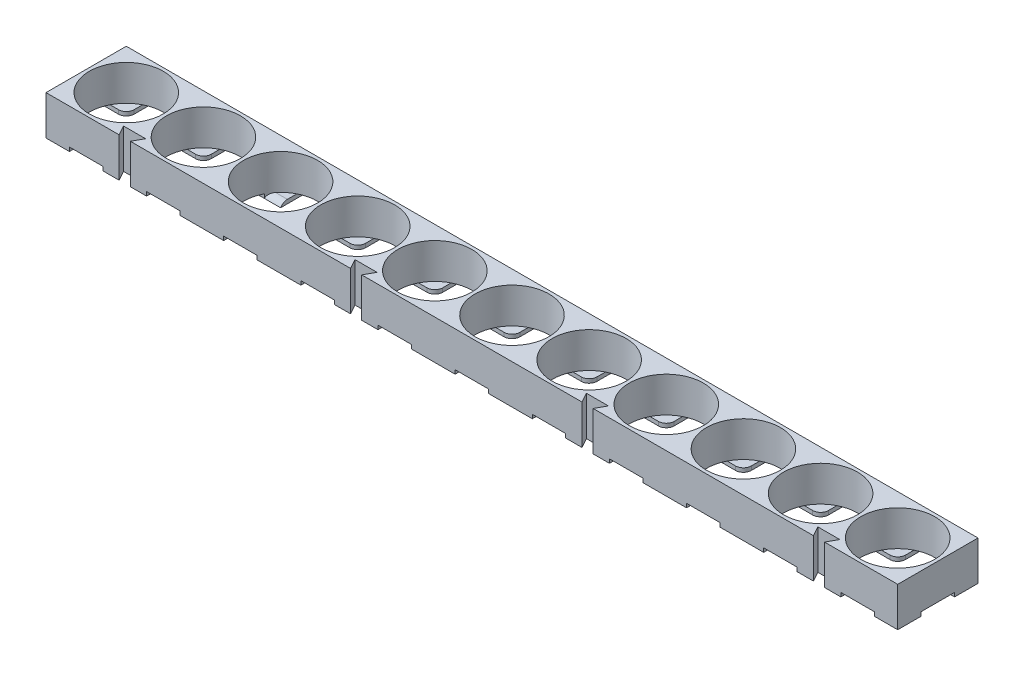
SolidWorks part; units mm, degrees
note: The reader was unsure of these and kept them because the rebuilt part matched: shared geometry of "Sketch3<4>".
ref_plane "Front Plane" through (0, 0, 0) normal (0, 0, 1) x (1, 0, 0)
ref_plane "Top Plane" through (0, 0, 0) normal (0, 1, 0) x (1, 0, 0)
ref_plane "Right Plane" through (0, 0, 0) normal (1, 0, 0) x (0, 0, -1)
sketch "Sketch3" plane through (0, 0, 0) normal (0, 1, 0) x (1, 0, 0)
  line L0 (-10.2, 0) -> (9.4, 0) construction
  line L5 (9.4, 9.4) -> (9.4, -9.4) construction
  line L6 (9.4, -9.4) -> (-9.4, -9.4) construction
  line L7 (-9.4, -9.4) -> (-9.4, 9.4) construction
  line L8 (-9.4, 9.4) -> (9.4, 9.4) construction
  line L9 (10.2, -9.4) -> (10.2, 9.4) construction
  line L10 (10.2, 9.4) -> (29, 9.4) construction
  line L11 (29, 9.4) -> (29, -9.4) construction
  line L12 (29, -9.4) -> (10.2, -9.4) construction
  line L13 (29.8, -9.4) -> (29.8, 9.4) construction
  line L14 (29.8, 9.4) -> (48.6, 9.4) construction
  line L15 (48.6, 9.4) -> (48.6, -9.4) construction
  line L16 (48.6, -9.4) -> (29.8, -9.4) construction
  line L17 (49.4, -9.4) -> (49.4, 9.4) construction
  line L18 (49.4, 9.4) -> (68.2, 9.4) construction
  line L19 (68.2, 9.4) -> (68.2, -9.4) construction
  line L20 (68.2, -9.4) -> (49.4, -9.4) construction
  line L21 (69, -9.4) -> (69, 9.4) construction
  line L22 (69, 9.4) -> (87.8, 9.4) construction
  line L23 (87.8, 9.4) -> (87.8, -9.4) construction
  line L24 (87.8, -9.4) -> (69, -9.4) construction
  line L25 (88.6, -9.4) -> (88.6, 9.4) construction
  line L26 (88.6, 9.4) -> (107.4, 9.4) construction
  line L27 (107.4, 9.4) -> (107.4, -9.4) construction
  line L28 (107.4, -9.4) -> (88.6, -9.4) construction
  line L29 (108.2, -9.4) -> (108.2, 9.4) construction
  line L30 (108.2, 9.4) -> (127, 9.4) construction
  line L31 (127, 9.4) -> (127, -9.4) construction
  line L32 (127, -9.4) -> (108.2, -9.4) construction
  line L33 (127.8, -9.4) -> (127.8, 9.4) construction
  line L34 (127.8, 9.4) -> (146.6, 9.4) construction
  line L35 (146.6, 9.4) -> (146.6, -9.4) construction
  line L36 (146.6, -9.4) -> (127.8, -9.4) construction
  line L37 (147.4, -9.4) -> (147.4, 9.4) construction
  line L38 (147.4, 9.4) -> (166.2, 9.4) construction
  line L39 (166.2, 9.4) -> (166.2, -9.4) construction
  line L40 (166.2, -9.4) -> (147.4, -9.4) construction
  line L41 (167, -9.4) -> (167, 9.4) construction
  line L42 (167, 9.4) -> (185.8, 9.4) construction
  line L43 (185.8, 9.4) -> (185.8, -9.4) construction
  line L44 (185.8, -9.4) -> (167, -9.4) construction
  line L45 (186.6, -9.4) -> (186.6, 9.4) construction
  line L46 (186.6, 9.4) -> (205.4, 9.4) construction
  line L47 (205.4, 9.4) -> (205.4, -9.4) construction
  line L48 (205.4, -9.4) -> (186.6, -9.4) construction
  line L49 (-10.2, 0) -> (206.2, 0) construction
  line L50 (-10.2, 10.2) -> (206.2, 10.2)
  line L51 (-10.2, 10.2) -> (-10.2, -10.2)
  line L52 (-10.2, -10.2) -> (206.2, -10.2)
  line L53 (206.2, 10.2) -> (206.2, -10.2)
  line L54 (9.4, 9.4) -> (10.2, 9.4) construction
  line L55 (9.8, 29) -> (9.8, -10.2) construction
  line L56 (68.2, 9.4) -> (69, 9.4) construction
  line L57 (68.6, 9.4) -> (68.6, 13.7208) construction
  line L58 (12.3, 12.4) -> (7.3, 12.4)
  line L59 (7.3, 12.4) -> (8.5702, 10.2)
  line L60 (8.5702, 10.2) -> (11.0298, 10.2)
  line L61 (12.3, 12.4) -> (11.0298, 10.2)
  line L62 (12.6, -7.7) -> (7, -7.7)
  line L63 (7, -7.7) -> (8.3858, -10.2)
  line L64 (8.3858, -10.2) -> (11.2142, -10.2)
  line L65 (12.6, -7.7) -> (11.2142, -10.2)
  line L66 (67.3702, 10.2) -> (69.8298, 10.2)
  line L67 (71.1, 12.4) -> (69.8298, 10.2)
  line L68 (71.1, 12.4) -> (66.1, 12.4)
  line L69 (66.1, 12.4) -> (67.3702, 10.2)
  line L70 (67.1858, -10.2) -> (70.0142, -10.2)
  line L71 (71.4, -7.7) -> (70.0142, -10.2)
  line L72 (71.4, -7.7) -> (65.8, -7.7)
  line L73 (65.8, -7.7) -> (67.1858, -10.2)
  line L74 (126.1702, 10.2) -> (128.6298, 10.2)
  line L75 (129.9, 12.4) -> (128.6298, 10.2)
  line L76 (129.9, 12.4) -> (124.9, 12.4)
  line L77 (124.9, 12.4) -> (126.1702, 10.2)
  line L78 (125.9858, -10.2) -> (128.8142, -10.2)
  line L79 (130.2, -7.7) -> (128.8142, -10.2)
  line L80 (130.2, -7.7) -> (124.6, -7.7)
  line L81 (124.6, -7.7) -> (125.9858, -10.2)
  line L82 (184.9702, 10.2) -> (187.4298, 10.2)
  line L83 (188.7, 12.4) -> (187.4298, 10.2)
  line L84 (188.7, 12.4) -> (183.7, 12.4)
  line L85 (183.7, 12.4) -> (184.9702, 10.2)
  line L86 (184.7858, -10.2) -> (187.6142, -10.2)
  line L87 (189, -7.7) -> (187.6142, -10.2)
  line L88 (189, -7.7) -> (183.4, -7.7)
  line L89 (183.4, -7.7) -> (184.7858, -10.2)
  line L90 (68.6, 12.4) -> (68.6, 10.2) construction
  circle A0 centre (0, 0) radius 9.4
  circle A1 centre (19.6, 0) radius 9.4
  circle A2 centre (39.2, 0) radius 9.4
  circle A3 centre (58.8, 0) radius 9.4
  circle A4 centre (78.4, 0) radius 9.4
  circle A5 centre (98, 0) radius 9.4
  circle A6 centre (117.6, 0) radius 9.4
  circle A7 centre (137.2, 0) radius 9.4
  circle A8 centre (156.8, 0) radius 9.4
  circle A9 centre (176.4, 0) radius 9.4
  circle A10 centre (196, 0) radius 9.4
  point P10 (-0.4, 0)
  point P13 (-9.4, 0)
  point P16 (0, 9.4)
  point P84 (9.8, 9.4)
  point P88 (9.8, 10.2)
  point P89 (9.8, 12.4)
  point P94 (9.8, -7.7)
  dimension "D1" = 18.8
  dimension "D2" = 11
  dimension "D3" = 0.8
  dimension "D4" = 0.8
  dimension "D5" = 0.8
  dimension "D6" = 0.8
  dimension "D7" = 216.4
  dimension "D8" = 20.4
  dimension "D9" = 5
  dimension "D10" = 60
  dimension "D11" = 2.2
  dimension "D12" = 5.6
  dimension "D13" = 61
  dimension "D14" = 2.5
  dimension "D15" = 4
extrude "Boss-Extrude3" add sketch "Sketch3" along normal blind 10 contours L89 L88 L87 L52 L53 L50 L51 L63 L62 L65 L73 L72 L71 L81 L80 L79 A10 A9 A8 A7 A6 A5 A4 A3 A2 A1 A0 | L61 L58 L59 L50 | L68 L69 L50 L67 | L76 L77 L50 L75 | L84 L85 L50 L83
extrude "Boss-Extrude6" add sketch "Sketch3<4>" along normal blind 1 contours A0 | A1 | A2 | A3 | A4 | A5 | A6 | A7 | A8 | A9 | A10
sketch "Sketch3<4>" plane through (0, 0, 0) normal (0, 1, 0) x (1, 0, 0) same geometry as "Sketch3"
sketch "Sketch8" plane through (0, 1, 0) normal (0, 1, 0) x (1, 0, 0)
  line L0 (-9.4, 0) -> (9.4, 0) construction
  line L1 (0, -9.4) -> (0, 9.4) construction
  line L2 (19.6, -9.4) -> (19.6, 9.4) construction
  line L3 (206.2, 10.2) -> (206.2, -10.2) construction
  line L4 (-10.2, -4.25) -> (206.2, -4.25)
  line L5 (-10.2, -4.25) -> (-10.2, 4.25)
  line L6 (-10.2, 4.25) -> (206.2, 4.25)
  line L7 (206.2, -4.25) -> (206.2, 4.25)
  line L8 (-10.2, -4.25) -> (206.2, 4.25) construction
  line L9 (-10.2, 4.25) -> (206.2, -4.25) construction
  line L10 (-10.2, 10.2) -> (8.5702, 10.2) construction
  line L11 (-4.25, -10.2) -> (4.25, -10.2)
  line L12 (-4.25, -10.2) -> (-4.25, 10.2)
  line L13 (-4.25, 10.2) -> (4.25, 10.2)
  line L14 (4.25, -10.2) -> (4.25, 10.2)
  line L15 (-4.25, -10.2) -> (4.25, 10.2) construction
  line L16 (-4.25, 10.2) -> (4.25, -10.2) construction
  line L17 (15.35, -10.2) -> (15.35, 10.2)
  line L18 (15.35, -10.2) -> (23.85, -10.2)
  line L19 (23.85, -10.2) -> (23.85, 10.2)
  line L20 (15.35, 10.2) -> (23.85, 10.2)
  line L21 (34.95, -10.2) -> (34.95, 10.2)
  line L22 (34.95, -10.2) -> (43.45, -10.2)
  line L23 (43.45, -10.2) -> (43.45, 10.2)
  line L24 (34.95, 10.2) -> (43.45, 10.2)
  line L25 (54.55, -10.2) -> (54.55, 10.2)
  line L26 (54.55, -10.2) -> (63.05, -10.2)
  line L27 (63.05, -10.2) -> (63.05, 10.2)
  line L28 (54.55, 10.2) -> (63.05, 10.2)
  line L29 (74.15, -10.2) -> (74.15, 10.2)
  line L30 (74.15, -10.2) -> (82.65, -10.2)
  line L31 (82.65, -10.2) -> (82.65, 10.2)
  line L32 (74.15, 10.2) -> (82.65, 10.2)
  line L33 (93.75, -10.2) -> (93.75, 10.2)
  line L34 (93.75, -10.2) -> (102.25, -10.2)
  line L35 (102.25, -10.2) -> (102.25, 10.2)
  line L36 (93.75, 10.2) -> (102.25, 10.2)
  line L37 (113.35, -10.2) -> (113.35, 10.2)
  line L38 (113.35, -10.2) -> (121.85, -10.2)
  line L39 (121.85, -10.2) -> (121.85, 10.2)
  line L40 (113.35, 10.2) -> (121.85, 10.2)
  line L41 (132.95, -10.2) -> (132.95, 10.2)
  line L42 (132.95, -10.2) -> (141.45, -10.2)
  line L43 (141.45, -10.2) -> (141.45, 10.2)
  line L44 (132.95, 10.2) -> (141.45, 10.2)
  line L45 (152.55, -10.2) -> (152.55, 10.2)
  line L46 (152.55, -10.2) -> (161.05, -10.2)
  line L47 (161.05, -10.2) -> (161.05, 10.2)
  line L48 (152.55, 10.2) -> (161.05, 10.2)
  line L49 (172.15, -10.2) -> (172.15, 10.2)
  line L50 (172.15, -10.2) -> (180.65, -10.2)
  line L51 (180.65, -10.2) -> (180.65, 10.2)
  line L52 (172.15, 10.2) -> (180.65, 10.2)
  line L53 (191.75, -10.2) -> (191.75, 10.2)
  line L54 (191.75, -10.2) -> (200.25, -10.2)
  line L55 (200.25, -10.2) -> (200.25, 10.2)
  line L56 (191.75, 10.2) -> (200.25, 10.2)
  line L57 (15.35, 10.2) -> (23.85, -10.2) construction
  circle A2 centre (0, 0) radius 9.4
  circle A3 centre (0, 0) radius 9.4 construction
  circle A5 centre (19.6, 0) radius 9.4
  circle A6 centre (19.6, 0) radius 9.4 construction
  point P3 (0, 0)
  point P12 (0, 0)
  point P14 (19.6, 0)
  point P15 (98, 0)
  point P29 (0, 0)
  dimension "D3" = 19.6
  dimension "D4" = 8.5
  dimension "D5" = 11
  dimension "D1" = 0
  dimension "D2" = 0
extrude "Cut-Extrude4" cut sketch "Sketch8" against normal through all contours L6 L7 L4 L5 | L12 L13 L14 L11 | L17 L20 L19 L18 | L21 L24 L23 L22 | L25 L28 L27 L26 | L29 L32 L31 L30 | L33 L36 L35 L34 | L37 L40 L39 L38 | L41 L44 L43 L42 | L45 L48 L47 L46 | L49 L52 L51 L50 | L53 L56 L55 L54
fillet "Fillet3" radius 2 44 edges at (4.25, 0.5, -4.25) (-4.25, 0.5, -4.25) (4.25, 0.5, 4.25) (-4.25, 0.5, 4.25) (191.75, 0.5, -4.25) (191.75, 0.5, 4.25) (172.15, 0.5, -4.25) (172.15, 0.5, 4.25) (152.55, 0.5, 4.25) (152.55, 0.5, -4.25) (132.95, 0.5, -4.25) (132.95, 0.5, 4.25) (113.35, 0.5, -4.25) (111.2828, 1, 4.25) (93.75, 0.5, 4.25) (93.75, 0.5, -4.25) (74.15, 0.5, 4.25) (74.15, 0.5, -4.25) (54.55, 0.5, -4.25) (54.55, 0.5, 4.25) (34.95, 0.5, 4.25) (32.8828, 1, -4.25) (63.05, 0.5, -4.25) (63.05, 0.5, 4.25) (82.65, 0.5, -4.25) (82.65, 0.5, 4.25) (102.25, 0.5, -4.25) (102.25, 0.5, 4.25) (121.85, 0.5, -4.25) (121.85, 0.5, 4.25) (141.45, 0.5, 4.25) (141.45, 0.5, -4.25) (161.05, 0.5, -4.25) (161.05, 0.5, 4.25) (180.65, 0.5, 4.25) (180.65, 0.5, -4.25) (200.25, 0.5, -4.25) (200.25, 0.5, 4.25) (43.45, 0.5, 4.25) (43.45, 0.5, -4.25) (23.85, 0.5, -4.25) (23.85, 0.5, 4.25) (15.35, 0.5, 4.25) (15.35, 0.5, -4.25)
sketch "Sketch9" plane through (0, 10, 0) normal (0, 1, 0) x (1, 0, 0)
  line L1 (-10.2, 10.2) -> (207.8849, 10.2)
  line L2 (-10.2, 10.2) -> (-10.2, 15.2624)
  line L3 (-10.2, 15.2624) -> (207.8849, 15.2624)
  line L4 (207.8849, 10.2) -> (207.8849, 15.2624)
extrude "Cut-Extrude5" cut sketch "Sketch9" against normal through all
equation "\"`\"=10"
